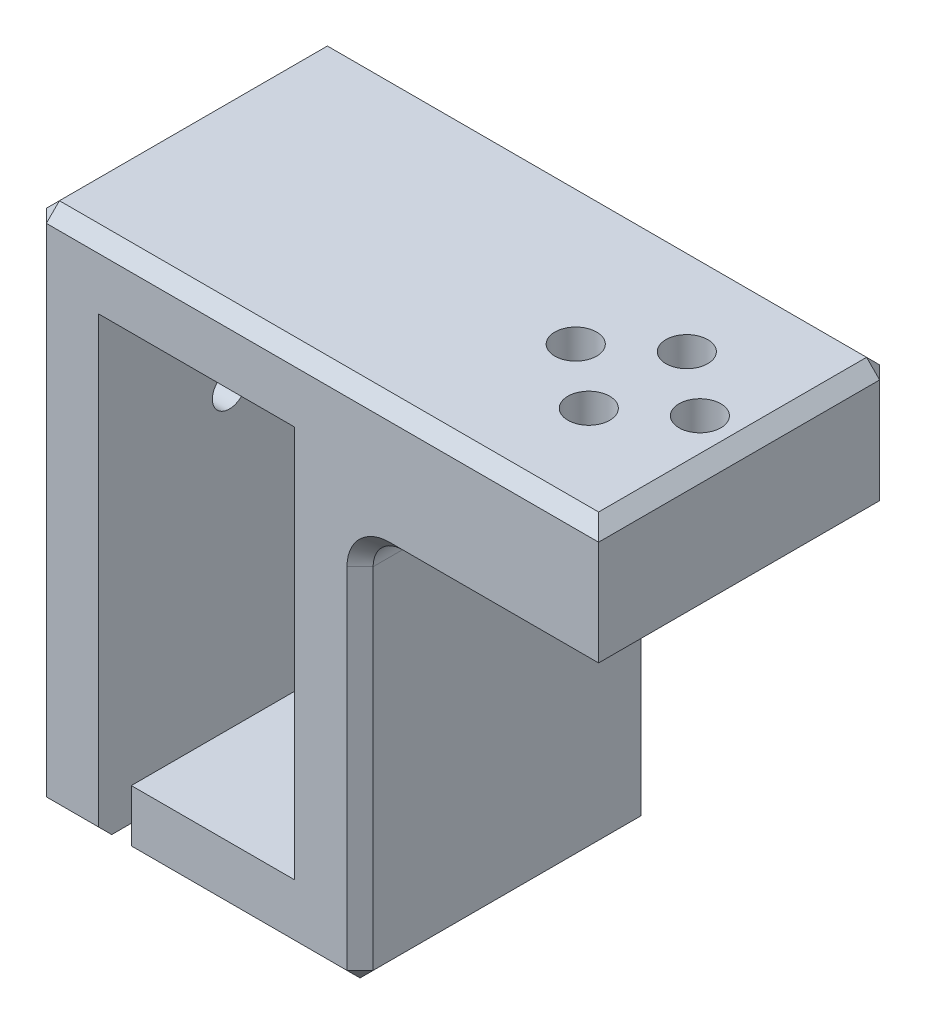
SolidWorks part; units mm, degrees
ref_plane "Płaszczyzna przednia" through (0, 0, 0) normal (0, 0, 1) x (1, 0, 0)
ref_plane "Płaszczyzna górna" through (0, 0, 0) normal (0, 1, 0) x (1, 0, 0)
ref_plane "Płaszczyzna prawa" through (0, 0, 0) normal (1, 0, 0) x (0, 0, -1)
sketch "Sketch1" plane through (0, 0, 0) normal (0, 0, 1) x (1, 0, 0)
  line L0 (10, 0) -> (0, 0)
  line L1 (0, 0) -> (0, 80)
  line L2 (0, 80) -> (50, 80)
  line L3 (50, 80) -> (50, 0)
  line L4 (50, 0) -> (15, 0)
  line L6 (40, 70) -> (10, 70)
  line L13 (10, 0) -> (10, 70)
  line L14 (40, 70) -> (40, 10)
  line L15 (40, 10) -> (15, 10)
  line L16 (15, 10) -> (15, 0)
  point P3 (40.8352, 0)
  point P10 (18.768, 0)
  dimension "D1" = 50
  dimension "D2" = 5
  dimension "D3" = 10
  dimension "D4" = 10
  dimension "D5" = 10
  dimension "D6" = 70
  dimension "D7" = 80
extrude "Boss-Extrude1" add sketch "Sketch1" along normal blind 40
sketch "Sketch2" plane through (0, 0, 0) normal (1, 0, 0) x (0, 0, -1)
  line L0 (-40, 0) -> (-40, 80) construction
  line L1 (-40, 0) -> (0, 0) construction
  circle A0 centre (-20, 50) radius 2.6
  dimension "D3" = 5.2
  dimension "D1" = 20
  dimension "D2" = 50
extrude "Cut-Extrude1" cut sketch "Sketch2" against normal through all from surface starting at face at (10, 35, 20)
sketch "Sketch9" plane through (0, 0, 0) normal (0, 0, 1) x (1, 0, 0)
  line L1 (50, 80) -> (0, 80)
  line L2 (50, 80) -> (50, 0)
  line L3 (50, 0) -> (0, 0)
  line L4 (0, 80) -> (0, 0)
extrude "Boss-Extrude2" add sketch "Sketch9" against normal blind 5
sketch "Sketch11" plane through (0, 0, 0) normal (0, 1, 0) x (1, 0, 0)
  line L0 (50, 5) -> (86.5, 5)
  line L1 (86.5, 5) -> (86.5, -40)
  line L2 (86.5, -40) -> (50, -40)
  line L3 (50, -40) -> (50, 5)
  line L8 (60.5, -17.5) -> (79.5, -17.5) construction
  line L9 (70, -17.5) -> (70, -10) construction
  line L10 (70, -17.5) -> (70, -25) construction
  line L11 (50, -40) -> (50, 5) construction
  circle A4 centre (60.5, -17.5) radius 3.2
  circle A5 centre (70, -10) radius 3.2
  circle A6 centre (79.5, -17.5) radius 3.2
  circle A7 centre (70, -25) radius 3.2
  dimension "D4" = 7.5
  dimension "D7" = 6.4
  dimension "D1" = 45
  dimension "D2" = 20
  dimension "D3" = 7.5
  dimension "D5" = 19
  dimension "D6" = 36.5
  dimension "D8" = 22.5
extrude "Boss-Extrude4" add sketch "Sketch11" against normal blind 20 from surface starting at face at (25, 80, 17.5)
sketch "Sketch12" plane through (0, 0, 0) normal (0, 1, 0) x (1, 0, 0)
  circle A0 centre (70, -10) radius 5.7
  circle A1 centre (79.5, -17.5) radius 5.7
  circle A2 centre (70, -25) radius 5.7
  circle A3 centre (60.5, -17.5) radius 5.7
  dimension "D1" = 11.4
extrude "Cut-Extrude11" cut sketch "Sketch12" along normal blind 5 from surface starting at face at (68.25, 60, 17.5)
fillet "Fillet1" radius 4.5 1 edges at (50, 60, 17.5)
chamfer "Chamfer1" distance 2 angle 45 19 edges at (50, 27.75, -5) (50, 27.75, 40) (51.318, 58.682, -5) (51.318, 58.682, 40) (0, 80, 17.5) (43.25, 80, -5) (0, 40, -5) (32.5, 0, 40) (5, 0, 40) (50, 0, 17.5) (25, 0, -5) (0, 0, 17.5) (0, 40, 40) (43.25, 80, 40) (86.5, 80, 17.5) (70.5, 60, -5) (86.5, 70, -5) (70.5, 60, 40) (86.5, 60, 17.5)
